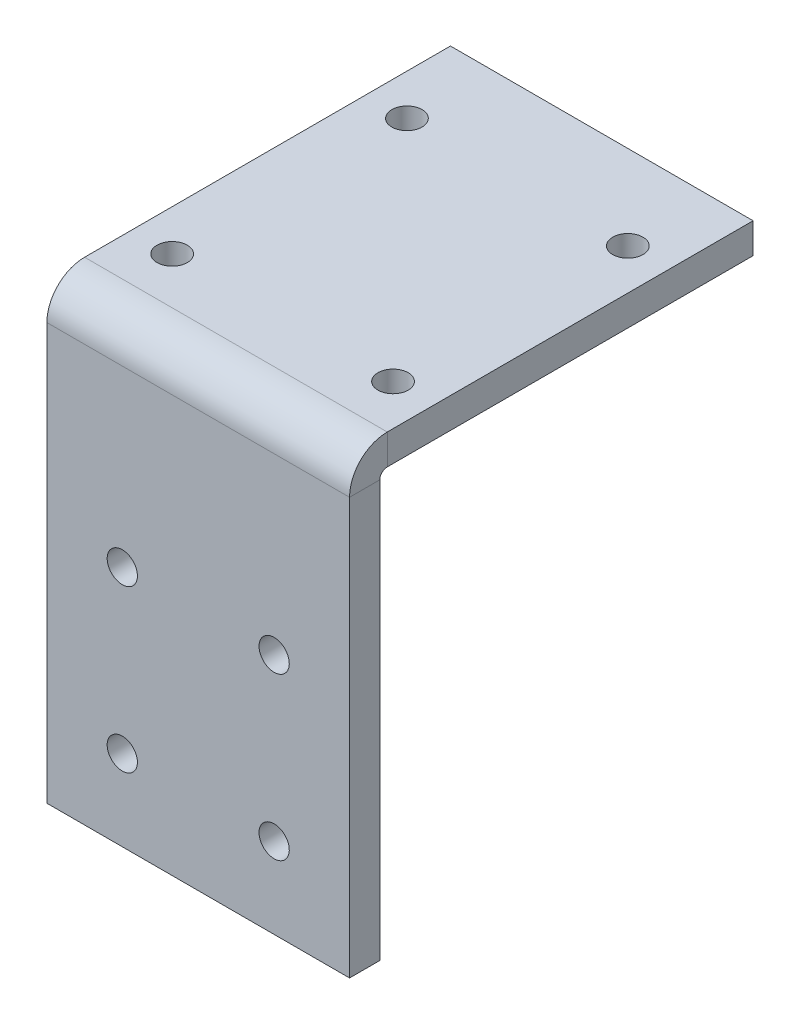
SolidWorks part; units mm, degrees
note: The reader was unsure of these and kept them because the rebuilt part matched: flange length of "Edge-Flange1".
ref_plane "Front Plane" through (0, 0, 0) normal (0, 0, 1) x (1, 0, 0)
ref_plane "Top Plane" through (0, 0, 0) normal (0, 1, 0) x (1, 0, 0)
ref_plane "Right Plane" through (0, 0, 0) normal (1, 0, 0) x (0, 0, -1)
sketch "Sketch1" plane through (0, 0, 0) normal (0, 1, 0) x (1, 0, 0)
  line L1 (-15, 20) -> (15, 20)
  line L2 (-15, 20) -> (-15, -20)
  line L3 (-15, -20) -> (15, -20)
  line L4 (15, 20) -> (15, -20)
  line L5 (-15, 20) -> (15, -20) construction
  line L6 (-15, -20) -> (15, 20) construction
  point P0 (0, 0)
  dimension "D1" = 30
  dimension "D2" = 40
base flange "Base-Flange1" sketch "Sketch1" thickness 3 reverse thickness direction no parameters "D1"=0.7366
edge flange "Edge-Flange1" sketch "Sketch8" flange angle 90 flange length 45 flange position material inside bend radius 0.7366 thickness 3 relief rectangular parameters "D6"=10
sketch "Sketch8" plane through (0, -3, 20) normal (0, 0, 1) x (-1, 0, 0)
  line L0 (15, 0) -> (-15, 0) construction
  line L1 (15, 0) -> (-15, 0)
  line L2 (-15, 0) -> (-15, 42)
  line L3 (-15, 42) -> (15, 42)
  line L4 (15, 42) -> (15, 0)
bend "EdgeBend1" bend radius 0.7366 bend angle 90 parameters "D5"=1
sketch "Sketch9" plane through (0, 0, 20) normal (0, 0, 1) x (1, 0, 0)
  line L0 (0, 0) -> (0, -45) construction
  line L1 (-15, -45) -> (15, -45) construction
  line L2 (-15, -3) -> (15, -3) construction
  circle A0 centre (-7.5257, -21) radius 1.5
  circle A1 centre (-7.5257, -37) radius 1.5
  circle A2 centre (7.5257, -37) radius 1.5
  circle A3 centre (7.5257, -21) radius 1.5
  dimension "D1" = 3
  dimension "D2" = 3
  dimension "D3" = 16
  dimension "D4" = 18
extrude "Cut-Extrude1" cut sketch "Sketch9" against normal blind 10 normal cut yes
sketch "Sketch10" plane through (0, -3, 0) normal (0, -1, 0) x (1, 0, 0)
  line L1 (0, -22) -> (0, 22) construction
  line L2 (16.5, 0) -> (-16.5, 0) construction
  circle A0 centre (-10.9475, 11.6351) radius 1.5
  circle A1 centre (10.9475, 11.6351) radius 1.5
  circle A2 centre (10.9475, -11.6351) radius 1.5
  circle A3 centre (-10.9475, -11.6351) radius 1.5
  dimension "D1" = 3
extrude "Cut-Extrude2" cut sketch "Sketch10" against normal blind 10 normal cut yes
sketch "Bend-Lines1" [suppressed] plane through (0, 0, 0) normal (0, 1, 0) x (1, 0, 0)
sketch "Bounding-Box1" [suppressed] plane through (0, 0, 0) normal (0, 1, 0) x (1, 0, 0)
sheet metal parameters "Sheet-Metal1" thickness 3 parameters "D1"=0.7366
flat pattern "Flat-Pattern1" [suppressed]
sketch "Bend-Lines2" plane through (0, 0, 0) normal (0, 1, 0) x (1, 0, 0)
sketch3d "Bounding-Box2" [suppressed]
  line L0 (15, 20, 0) -> (15, -20, 0) construction
  line L1 (-15, 20, 0) -> (-15, -20, 0) construction
  line L2 (15, 20, 0) -> (-15, 20, 0) construction
  line L3 (15, -20, 0) -> (-15, -20, 0) construction
sheet metal parameters "Sheet-Metal2" thickness 3 parameters "D1"=0.7366
flat pattern "Flat-Pattern1"
sketch "Bend-Lines2" plane through (0, 0, 0) normal (0, 1, 0) x (1, 0, 0)
  line L0 (-15, -18.02) -> (15, -18.02) construction
  line L1 (-15, -18.02) -> (15, -18.02) construction
sketch3d "Bounding-Box2" [suppressed]
  line L0 (-15, 20, 0) -> (-15, -56.04, 0) construction
  line L1 (15, 20, 0) -> (15, -56.04, 0) construction
  line L2 (-15, 20, 0) -> (15, 20, 0) construction
  line L3 (-15, -56.04, 0) -> (15, -56.04, 0) construction
bend of the flat pattern "Flatten-<EdgeBend1>1"
sheet metal parameters "Sheet-Metal3" thickness 3 parameters "D1"=0.7366
flat pattern "Flat-Pattern1"
sketch "Bend-Lines2" plane through (0, 0, 0) normal (0, 1, 0) x (1, 0, 0)
  line L0 (-15, -18.02) -> (15, -18.02) construction
  line L1 (-15, -18.02) -> (15, -18.02) construction
sketch3d "Bounding-Box2" [suppressed]
  line L0 (-15, 20, 0) -> (-15, -56.04, 0) construction
  line L1 (15, 20, 0) -> (15, -56.04, 0) construction
  line L2 (-15, 20, 0) -> (15, 20, 0) construction
  line L3 (-15, -56.04, 0) -> (15, -56.04, 0) construction
bend of the flat pattern "Flatten-<EdgeBend1>1"
sheet metal parameters "Sheet-Metal4" thickness 3 parameters "D1"=0.7366
flat pattern "Flat-Pattern1"
sketch "Bend-Lines2" plane through (0, 0, 0) normal (0, 1, 0) x (1, 0, 0)
  line L0 (-15, -18.02) -> (15, -18.02) construction
  line L1 (-15, -18.02) -> (15, -18.02) construction
sketch3d "Bounding-Box2" [suppressed]
  line L0 (-15, 20, 0) -> (-15, -61.04, 0) construction
  line L1 (15, 20, 0) -> (15, -61.04, 0) construction
  line L2 (-15, 20, 0) -> (15, 20, 0) construction
  line L3 (-15, -61.04, 0) -> (15, -61.04, 0) construction
bend of the flat pattern "Flatten-<EdgeBend1>1"
